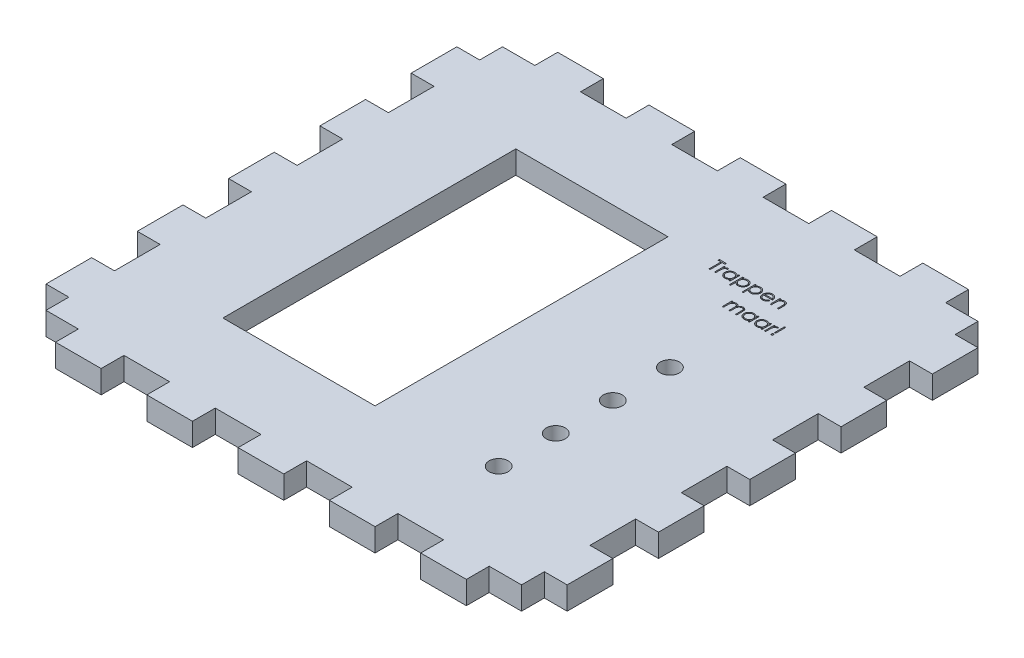
SolidWorks part; units mm, degrees
ref_plane "Front Plane" through (0, 0, 0) normal (0, 0, 1) x (1, 0, 0)
ref_plane "Top Plane" through (0, 0, 0) normal (0, 1, 0) x (1, 0, 0)
ref_plane "Right Plane" through (0, 0, 0) normal (1, 0, 0) x (0, 0, -1)
sketch "Sketch1" plane through (0, 0, 0) normal (0, 1, 0) x (1, 0, 0)
  line L0 (2.5, 38.5) -> (2.5, 60) construction
  line L1 (-62.5, -60) -> (62.5, -60)
  line L2 (-62.5, -60) -> (-62.5, 60)
  line L3 (-62.5, 60) -> (62.5, 60)
  line L4 (62.5, -60) -> (62.5, 60)
  line L5 (-62.5, -60) -> (62.5, 60) construction
  line L6 (-62.5, 60) -> (62.5, -60) construction
  line L7 (-37.5, -38.5) -> (2.5, -38.5)
  line L8 (-37.5, -38.5) -> (-37.5, 38.5)
  line L9 (-37.5, 38.5) -> (2.5, 38.5)
  line L10 (2.5, -38.5) -> (2.5, 38.5)
  line L11 (-37.5, -38.5) -> (2.5, 38.5) construction
  line L12 (-37.5, 38.5) -> (2.5, -38.5) construction
  line L13 (2.5, -38.5) -> (2.5, -60) construction
  line L14 (-37.5, 38.5) -> (-62.5, 38.5) construction
  line L15 (32.5, -36) -> (32.5, -21) construction
  line L16 (2.5, -38.5) -> (32.5, -38.5) construction
  line L17 (32.5, -21) -> (32.5, -6) construction
  line L18 (32.5, -6) -> (32.5, 9) construction
  line L19 (32.5, -38.5) -> (62.5, -38.5) construction
  line L20 (-54, 66) -> (-54, 60)
  line L21 (-62.5, 54) -> (-68.5, 54)
  line L22 (-54, 66) -> (-42, 66)
  line L23 (-42, 66) -> (-42, 60)
  line L24 (-18, 66) -> (-18, 60)
  line L25 (-30, 66) -> (-30, 60)
  line L26 (-30, 66) -> (-18, 66)
  line L27 (6, 66) -> (6, 60)
  line L28 (-6, 66) -> (-6, 60)
  line L29 (-6, 66) -> (6, 66)
  line L30 (30, 66) -> (30, 60)
  line L31 (18, 66) -> (18, 60)
  line L32 (18, 66) -> (30, 66)
  line L33 (54, 66) -> (54, 60)
  line L34 (42, 66) -> (42, 60)
  line L35 (42, 66) -> (54, 66)
  line L36 (-68.5, 54) -> (-68.5, 42)
  line L37 (-68.5, 42) -> (-62.5, 42)
  line L38 (-62.5, 30) -> (-68.5, 30)
  line L39 (-68.5, 30) -> (-68.5, 18)
  line L40 (-68.5, 18) -> (-62.5, 18)
  line L41 (-62.5, 6) -> (-68.5, 6)
  line L42 (-68.5, 6) -> (-68.5, -6)
  line L43 (-68.5, -6) -> (-62.5, -6)
  line L44 (-62.5, -18) -> (-68.5, -18)
  line L45 (-68.5, -18) -> (-68.5, -30)
  line L46 (-68.5, -30) -> (-62.5, -30)
  line L47 (-62.5, -42) -> (-68.5, -42)
  line L48 (-68.5, -42) -> (-68.5, -54)
  line L49 (-68.5, -54) -> (-62.5, -54)
  line L51 (0, -55) -> (0, 55) construction
  line L52 (68.5, -54) -> (62.5, -54)
  line L53 (68.5, -42) -> (68.5, -54)
  line L54 (62.5, -42) -> (68.5, -42)
  line L55 (68.5, -30) -> (62.5, -30)
  line L56 (68.5, -18) -> (68.5, -30)
  line L57 (62.5, -18) -> (68.5, -18)
  line L58 (68.5, -6) -> (62.5, -6)
  line L59 (68.5, 6) -> (68.5, -6)
  line L60 (62.5, 6) -> (68.5, 6)
  line L61 (68.5, 18) -> (62.5, 18)
  line L62 (68.5, 30) -> (68.5, 18)
  line L63 (62.5, 30) -> (68.5, 30)
  line L64 (68.5, 42) -> (62.5, 42)
  line L65 (68.5, 54) -> (68.5, 42)
  line L66 (-55, 0) -> (55, 0) construction
  line L67 (42, -66) -> (54, -66)
  line L68 (42, -66) -> (42, -60)
  line L69 (54, -66) -> (54, -60)
  line L70 (18, -66) -> (30, -66)
  line L71 (18, -66) -> (18, -60)
  line L72 (30, -66) -> (30, -60)
  line L73 (-6, -66) -> (6, -66)
  line L74 (-6, -66) -> (-6, -60)
  line L75 (6, -66) -> (6, -60)
  line L76 (-30, -66) -> (-18, -66)
  line L77 (-30, -66) -> (-30, -60)
  line L78 (-18, -66) -> (-18, -60)
  line L79 (-42, -66) -> (-42, -60)
  line L80 (-54, -66) -> (-42, -66)
  line L81 (-54, -66) -> (-54, -60)
  line L82 (62.5, 54) -> (68.5, 54)
  circle A0 centre (32.5, 9) radius 2.5
  circle A1 centre (32.5, -6) radius 2.5
  circle A2 centre (32.5, -21) radius 2.5
  circle A3 centre (32.5, -36) radius 2.5
  point P0 (0, 0)
  point P6 (-17.5, 0)
  dimension "D7" = 6
  dimension "D8" = 12
  dimension "D1" = 125
  dimension "D2" = 5
  dimension "D4" = 40
  dimension "D5" = 25
  dimension "D10" = 8.5
  dimension "D12" = 12
  dimension "D13" = 6
  dimension "D14" = 6
  dimension "D11" = 5
extrude "Boss-Extrude2" add sketch "Sketch1" along normal blind 6 contours L1 L4 L3 L2 A3 A2 A1 | L39 L40 L2 L38 | L36 L37 L2 L21 | L45 L46 L2 L44 | L42 L43 L2 L41 | L48 L49 L2 L47 | L81 L80 L79 L1 | L76 L78 L1 L77 | L73 L75 L1 L74 | L70 L72 L1 L71 | L67 L69 L1 L68 | L54 L4 L52 L53 | L57 L4 L55 L56 | L60 L4 L58 L59 | L63 L4 L61 L62 | L82 L4 L64 L65 | L35 L34 L3 L33 | L32 L31 L3 L30 | L29 L28 L3 L27 | L23 L22 L20 L3 | L26 L25 L3 L24 region at (4.3362, 0, -0.0895) region at (-48, 0, 63) region at (-65.5, 0, 48) region at (-24, 0, 63) region at (-65.5, 0, 24) region at (0, 0, 63) region at (-65.5, 0, 0) region at (24, 0, 63) region at (-65.5, 0, -24) region at (48, 0, 63) region at (-65.5, 0, -48) region at (65.5, 0, 48) region at (-48, 0, -63) region at (65.5, 0, 24) region at (-24, 0, -63) region at (65.5, 0, 0) region at (0, 0, -63) region at (65.5, 0, -24) region at (24, 0, -63) region at (65.5, 0, -48) region at (48, 0, -63)
sketch "Sketch2" plane through (0, 6, 0) normal (0, 1, 0) x (1, 0, 0)
  text T0 "Trappen \r\n        maar!" font "Century Gothic" height 3.5
extrude "Cut-Extrude1" cut sketch "Sketch2" against normal through all
